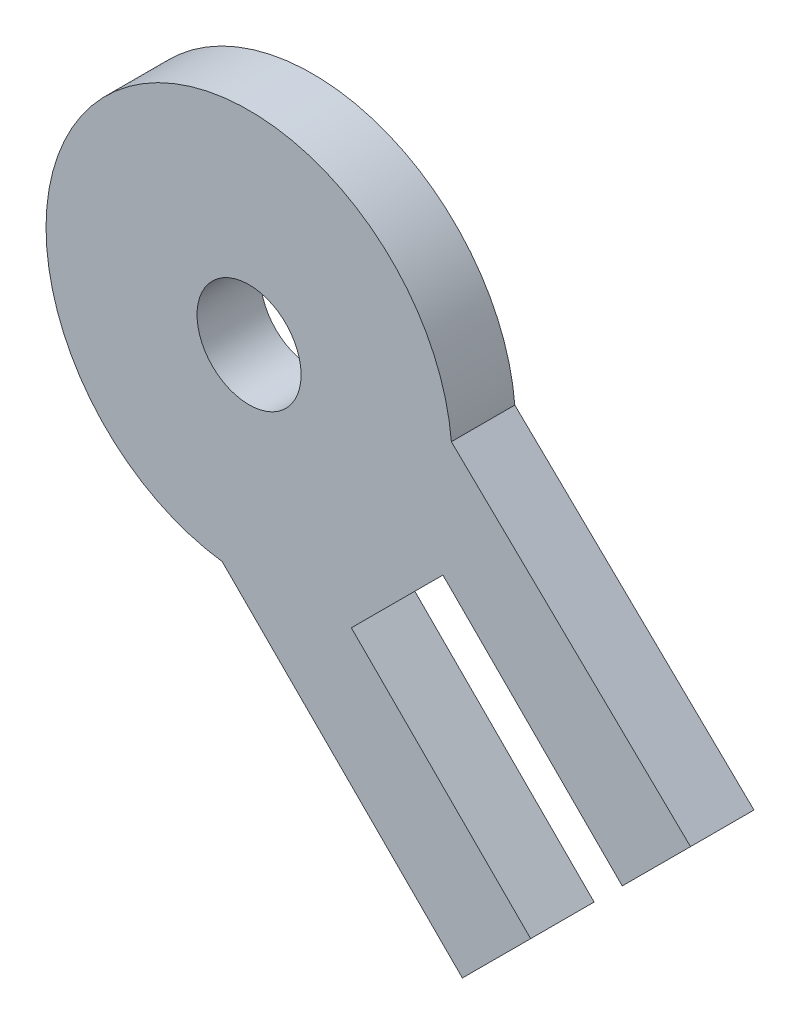
SolidWorks part; units mm, degrees
ref_plane "Front Plane" through (0, 0, 0) normal (0, 0, 1) x (1, 0, 0)
ref_plane "Top Plane" through (0, 0, 0) normal (0, 1, 0) x (1, 0, 0)
ref_plane "Right Plane" through (0, 0, 0) normal (1, 0, 0) x (0, 0, -1)
sketch "Sketch2" plane through (0, 0, 0) normal (0, 0, 1) x (1, 0, 0)
  line L6 (111.0088, 451.8451) -> (92.1603, 470.0568)
  line L7 (96.7422, 455.2278) -> (229.7591, 322.0245) construction
  line L8 (98.4101, 439.264) -> (84.2778, 453.416)
  line L9 (84.2778, 453.416) -> (91.4954, 460.6235)
  line L10 (91.4954, 460.6235) -> (105.6276, 446.4715)
  line L13 (93.0289, 433.8903) -> (98.4101, 439.264)
  line L14 (105.6276, 446.4715) -> (111.0088, 451.8451)
  line L16 (74.0997, 452.846) -> (93.0289, 433.8903)
  line L18 (76.2175, 468.7053) -> (96.3107, 448.5839) construction
  line L19 (84.3486, 453.4867) -> (89.6662, 448.1617) construction
  line L20 (84.3486, 453.4867) -> (91.4246, 460.5528) construction
  arc A1 (92.1603, 470.0568) -> (74.0997, 452.846) centre (76.2175, 468.7053) ccw
  circle A2 centre (76.2175, 468.7053) radius 5
  point P20 (92.1215, 470.4548)
  point P21 (74.2075, 452.832)
  circle M16 centre (76.2175, 468.7053) radius 4.1
  dimension "D1" = 10.2
  dimension "D3" = 10
  dimension "D4" = 16
  dimension "D2" = 0.1
  dimension "D5" = 20
extrude "Boss-Extrude1" add sketch "Sketch2" along normal blind 5 contours M16 | L16 L13 L8 L9 L10 L14 L6 A1 region at (76.2175, 468.7053, 0)
